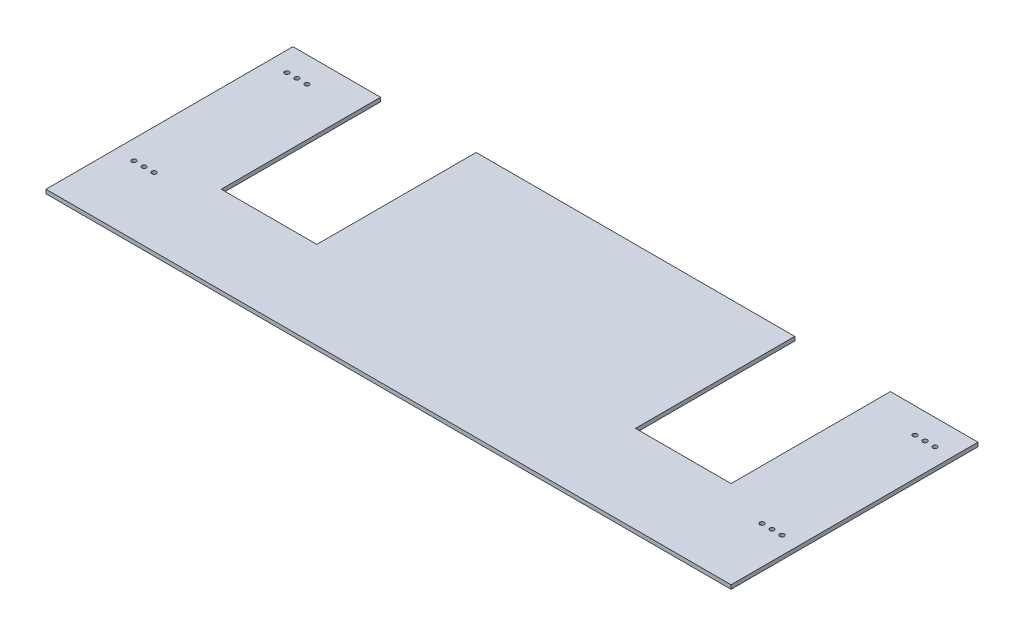
SolidWorks part; units mm, degrees
ref_plane "Front Plane" through (0, 0, 0) normal (0, 0, 1) x (1, 0, 0)
ref_plane "Top Plane" through (0, 0, 0) normal (0, 1, 0) x (1, 0, 0)
ref_plane "Right Plane" through (0, 0, 0) normal (1, 0, 0) x (0, 0, -1)
sketch "Sketch1" plane through (0, 0, 0) normal (0, 0, 1) x (1, 0, 0)
  line L1 (-273.05, -1.5875) -> (273.05, -1.5875)
  line L2 (-273.05, -1.5875) -> (-273.05, 1.5875)
  line L3 (-273.05, 1.5875) -> (273.05, 1.5875)
  line L4 (273.05, -1.5875) -> (273.05, 1.5875)
  line L5 (-273.05, -1.5875) -> (273.05, 1.5875) construction
  line L6 (-273.05, 1.5875) -> (273.05, -1.5875) construction
  point P0 (0, 0)
  dimension "D1" = 3.175
  dimension "D2" = 546.1
extrude "Boss-Extrude1" add sketch "Sketch1" along normal blind 184.15
sketch "Sketch2" plane through (0, 1.5875, 0) normal (0, 1, 0) x (1, 0, 0)
  line L0 (-257.556, -7.62) -> (-249.555, -7.62) construction
  line L1 (-257.556, -7.62) -> (-257.556, -5.842)
  line L2 (-257.556, -5.842) -> (-257.556, -7.62)
  line L3 (-259.334, -7.62) -> (-257.556, -7.62)
  line L4 (273.05, 0) -> (-273.05, 0) construction
  line L5 (-273.05, -184.15) -> (-273.05, 0) construction
  line L6 (0, 0) -> (0, -184.15)
  line L7 (273.05, -184.15) -> (-273.05, -184.15) construction
  line L8 (259.08, -129.54) -> (251.079, -129.54) construction
  line L11 (-273.05, -68.58) -> (273.05, -68.58)
  line L12 (259.08, -129.54) -> (259.08, -131.318)
  line L13 (-257.556, -9.398) -> (-257.556, -7.62)
  line L14 (-257.556, -7.62) -> (-257.556, -9.398)
  line L15 (273.05, -184.15) -> (273.05, 0) construction
  line L18 (259.08, -131.318) -> (259.08, -129.54)
  line L19 (-257.556, -129.54) -> (-249.555, -129.54) construction
  line L20 (-257.556, -129.54) -> (-257.556, -127.762)
  line L21 (-257.556, -127.762) -> (-257.556, -129.54)
  line L22 (-259.334, -129.54) -> (-257.556, -129.54)
  line L23 (-257.556, -131.318) -> (-257.556, -129.54)
  line L24 (-257.556, -129.54) -> (-257.556, -131.318)
  line L25 (260.858, -129.54) -> (259.08, -129.54)
  line L26 (259.08, -127.762) -> (259.08, -129.54)
  line L27 (259.08, -129.54) -> (259.08, -127.762)
  line L28 (259.08, -7.62) -> (251.079, -7.62) construction
  line L29 (259.08, -7.62) -> (259.08, -9.398)
  line L30 (259.08, -9.398) -> (259.08, -7.62)
  line L31 (260.858, -7.62) -> (259.08, -7.62)
  line L32 (259.08, -5.842) -> (259.08, -7.62)
  line L33 (259.08, -7.62) -> (259.08, -5.842)
  line L34 (-239.776, -129.54) -> (241.3, -129.54)
  circle A5 centre (-257.556, -7.62) radius 1.778
  circle A13 centre (-249.555, -7.62) radius 1.778
  circle A14 centre (-241.554, -7.62) radius 1.778
  circle A18 centre (-241.554, -129.54) radius 1.778
  circle A19 centre (-249.555, -129.54) radius 1.778
  circle A20 centre (-257.556, -129.54) radius 1.778
  circle A21 centre (259.08, -129.54) radius 1.778
  circle A22 centre (251.079, -129.54) radius 1.778
  circle A23 centre (243.078, -129.54) radius 1.778
  circle A24 centre (243.078, -7.62) radius 1.778
  circle A25 centre (251.079, -7.62) radius 1.778
  circle A26 centre (259.08, -7.62) radius 1.778
  dimension "D1" = 5.842
  dimension "D2" = 3.556
  dimension "D4" = 3
  dimension "D5" = 68.58
  dimension "D7" = 3.556
  dimension "D3" = 3.556
  dimension "D8" = 3.556
  dimension "D9" = 3.556
  dimension "D10" = 8.001
  dimension "D11" = 8.001
  dimension "D12" = 13.97
  dimension "D13" = 3.556
  dimension "D14" = 3.556
  dimension "D15" = 8.001
  dimension "D16" = 8.001
  dimension "D17" = 15.494
  dimension "D18" = 3.556
  dimension "D19" = 3.556
  dimension "D20" = 3.556
  dimension "D21" = 8.001
  dimension "D22" = 8.001
  dimension "D23" = 13.97
  dimension "D6" = 8.001
extrude "Cut-Extrude2" cut sketch "Sketch2" against normal through all contours A22 | A5 | A13 | A14 | A18 | A20 | A19 | A24 | A26 | A25 | A21 | A23
sketch "Sketch3" plane through (0, 1.5875, 0) normal (0, 1, 0) x (1, 0, 0)
  line L0 (-273.05, -184.15) -> (-273.05, 0) construction
  line L1 (-273.05, -42.9615) -> (273.05, -42.9615)
  line L2 (-273.05, -42.9615) -> (-273.05, -55.6615)
  line L3 (-273.05, -55.6615) -> (273.05, -55.6615)
  line L4 (273.05, -42.9615) -> (273.05, -55.6615)
  line L5 (273.05, -184.15) -> (273.05, 0) construction
  dimension "D1" = 12.7
sketch "Sketch5" plane through (0, 0, 0) normal (0, 0, -1) x (-1, 0, 0)
  line L1 (-273.05, 1.5875) -> (273.05, 1.5875)
  line L2 (-273.05, 1.5875) -> (-273.05, -1.5875)
  line L3 (-273.05, -1.5875) -> (273.05, -1.5875)
  line L4 (273.05, 1.5875) -> (273.05, -1.5875)
extrude "Boss-Extrude2" add sketch "Sketch5" along normal blind 12.7 contours L2 L1 L4 L3
sketch "Sketch6" plane through (0, 1.5875, 0) normal (0, 1, 0) x (1, 0, 0)
  line L0 (273.05, 12.7) -> (-273.05, 12.7) construction
  line L1 (-203.2, 12.7) -> (-127, 12.7)
  line L2 (-203.2, 12.7) -> (-203.2, -114.3)
  line L3 (-203.2, -114.3) -> (-127, -114.3)
  line L4 (-127, 12.7) -> (-127, -114.3)
  line L5 (0, 12.7) -> (0, -184.15)
  line L6 (127, 12.7) -> (203.2, 12.7)
  line L7 (127, 12.7) -> (127, -114.3)
  line L8 (127, -114.3) -> (203.2, -114.3)
  line L9 (203.2, 12.7) -> (203.2, -114.3)
  line L10 (273.05, -184.15) -> (-273.05, -184.15) construction
  line M12 (273.05, 12.7) -> (-273.05, 12.7)
  dimension "D1" = 127
  dimension "D2" = 76.2
  dimension "D3" = 127
  dimension "D4" = 127
  dimension "D5" = 76.2
  dimension "D6" = 127
extrude "Cut-Extrude4" cut sketch "Sketch6" against normal through all contours L4 L2 L3 M12 | L9 L7 L8 M12 region at (165.1, 1.5875, 50.8) region at (-165.1, 1.5875, 50.8)
